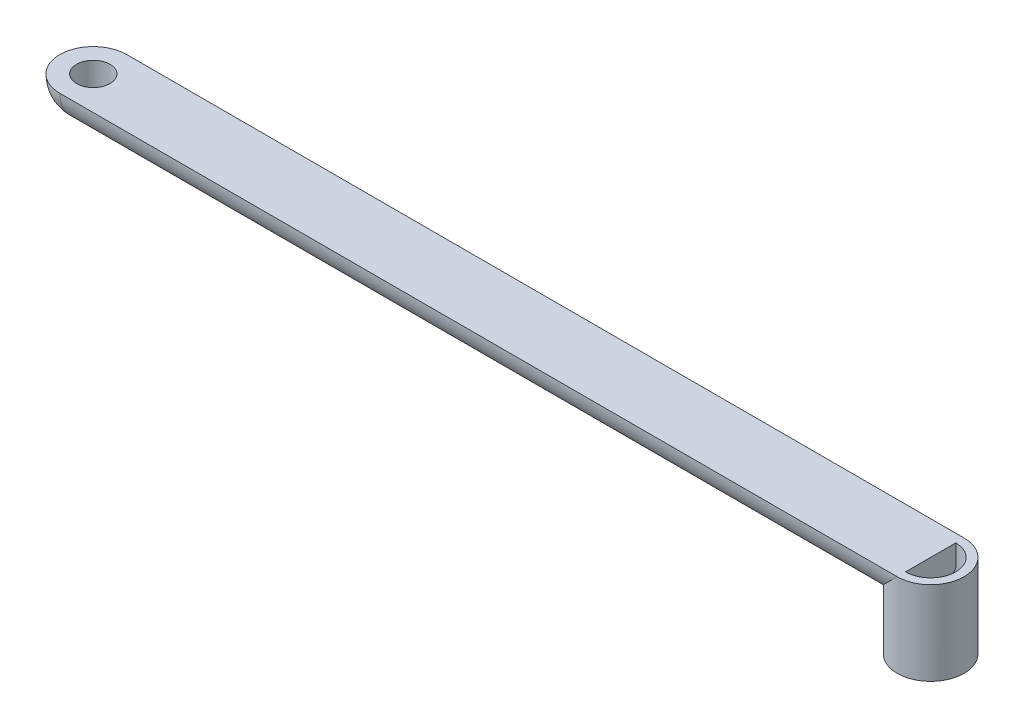
SolidWorks part; units mm, degrees
ref_plane "前视基准面" through (0, 0, 0) normal (0, 0, 1) x (1, 0, 0)
ref_plane "上视基准面" through (0, 0, 0) normal (0, 1, 0) x (1, 0, 0)
ref_plane "右视基准面" through (0, 0, 0) normal (1, 0, 0) x (0, 0, -1)
sketch "草图1" plane through (0, 0, 0) normal (0, 0, 1) x (1, 0, 0)
  line L0 (0, 0) -> (15, 0)
  line L1 (15, 0) -> (20, 0)
  line L2 (20, 0) -> (20, 50)
  line L3 (20, 50) -> (0, 50)
  line L4 (0, 50) -> (0, 0)
  line L5 (15, 0) -> (15, 50)
  line L6 (0, 50) -> (-500, 50)
  line L7 (-500, 50) -> (-500, 30)
  line L8 (-500, 30) -> (15, 30)
  line L9 (-500, 30) -> (-500, 230)
  line L10 (-500, 230) -> (-479.9639, 230)
  line L11 (-479.9639, 230) -> (-479.9639, 30)
  line L12 (-489.982, 230) -> (-489.982, 195)
  line L13 (-489.982, 195) -> (-479.9639, 195)
  line L14 (0, 0) -> (0, -10)
  line L15 (0, -10) -> (15, -10)
  line L16 (15, -10) -> (20, -10)
  line L17 (20, -10) -> (20, 0)
  line L18 (15, 0) -> (15, -10)
  circle A0 centre (-500, 50) radius 20
  dimension "D1" = 5
  dimension "D2" = 15
revolve "旋转1" add sketch "草图1" angle 360 about L4 region at (17.5, 25, 0)
revolve "旋转2" add sketch "草图1<3>" angle 90 about L6 region at (-239.982, 40, 0) region at (-484.43, 34.5135, 0) other way angle 90
sketch "草图1<3>" plane through (0, 0, 0) normal (0, 0, 1) x (1, 0, 0) same geometry as "草图1"
revolve "旋转4" add sketch "草图1<5>" angle 360 about L7 region at (-491.5117, 41.5117, 0)
sketch "草图1<5>" plane through (0, 0, 0) normal (0, 0, 1) x (1, 0, 0) same geometry as "草图1"
sketch "草图2" plane through (0, 50, 0) normal (0, 1, 0) x (1, 0, 0)
  circle A0 centre (-500, 0) radius 10
extrude "切除-拉伸1" cut sketch "草图2" against normal blind 31
